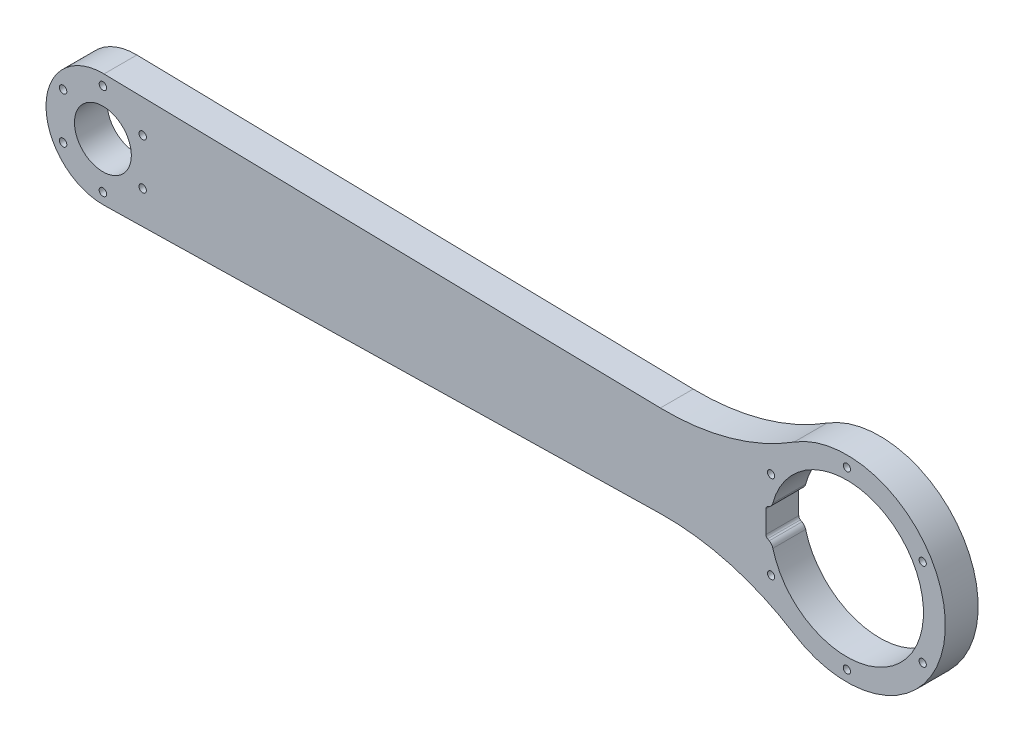
SolidWorks part; units mm, degrees
ref_plane "前视基准面" through (0, 0, 0) normal (0, 0, 1) x (1, 0, 0)
ref_plane "上视基准面" through (0, 0, 0) normal (0, 1, 0) x (1, 0, 0)
ref_plane "右视基准面" through (0, 0, 0) normal (1, 0, 0) x (0, 0, -1)
sketch "草图1" plane through (0, 0, 0) normal (0, 0, 1) x (1, 0, 0)
  line L0 (0, 0) -> (0, 46.9214) construction
  line L1 (0, 0) -> (75.8039, 0) construction
  line L2 (-85.2451, 20.9004) -> (-339.4791, 25.9948)
  line L3 (-85.2451, -20.9004) -> (-339.4791, -25.9948)
  line L4 (-35.5001, 6.7904) -> (-36.238, 6.3734)
  line L5 (-37, 5.0675) -> (-37, -5.0675)
  line L7 (-358.1865, 10.5) -> (-358.1865, -10.5) construction
  line L8 (-30.9669, 5.9447) -> (-28.6669, 5.9455) construction
  line L9 (-35.5001, -6.7904) -> (-36.238, -6.3734)
  line L10 (-29.6741, 7.5384) -> (-26.4741, 7.5394) construction
  line L11 (-340, -21) -> (-321.8135, -10.5) construction
  line L12 (-321.8135, -10.5) -> (-321.8135, 10.5) construction
  line L13 (-321.8135, 10.5) -> (-340, 21) construction
  line L14 (-340, 21) -> (-358.1865, 10.5) construction
  line L15 (-358.1865, -10.5) -> (-340, -21) construction
  circle A0 centre (0, 40) radius 1.65
  arc A1 (0, 38.35) -> (0, 41.65) centre (0, 40) ccw construction
  circle A2 centre (34.641, 20) radius 1.65
  circle A3 centre (34.641, -20) radius 1.65
  arc A4 (34.641, 18.35) -> (34.641, 21.65) centre (34.641, 20) ccw construction
  circle A5 centre (0, -40) radius 1.65
  arc A6 (0, -41.65) -> (0, -38.35) centre (0, -40) ccw construction
  circle A7 centre (-34.641, 20) radius 1.65
  arc A8 (-34.641, 21.65) -> (-34.641, 18.35) centre (-34.641, 20) ccw construction
  circle A9 centre (-34.641, -20) radius 1.65
  circle A10 centre (0, 0) radius 35 construction
  arc A12 (-33.8381, 8.9432) -> (-33.8381, -8.9432) centre (0, 0) cw
  arc A13 (-24.1088, 37.9969) -> (-24.1088, -37.9969) centre (0, 0) cw
  circle A14 centre (-340, 0) radius 13
  arc A15 (-85.2451, -20.9004) -> (-24.1088, -37.9969) centre (-83.0414, -130.8783) cw
  arc A16 (-24.1088, 37.9969) -> (-85.2451, 20.9004) centre (-83.0414, 130.8783) cw
  arc A17 (-339.4791, 25.9948) -> (-339.4791, -25.9948) centre (-340, 0) ccw
  arc A18 (-35.5001, -6.7904) -> (-33.8381, -8.9432) centre (-37.2219, -9.8375) cw
  arc A19 (-33.8381, 8.9432) -> (-35.5001, 6.7904) centre (-37.2219, 9.8375) cw
  arc A20 (-36.238, -6.3734) -> (-37, -5.0675) centre (-35.5, -5.0675) cw
  arc A21 (-36.238, 6.3734) -> (-37, 5.0675) centre (-35.5, 5.0675) ccw
  circle A22 centre (-340, 0) radius 21 construction
  circle A23 centre (-340, 0) radius 18.1865 construction
  circle A24 centre (-340, 21) radius 1.7
  circle A25 centre (-358.1865, 10.5) radius 1.7
  circle A26 centre (-358.1865, -10.5) radius 1.7
  circle A27 centre (-340, -21) radius 1.7
  circle A28 centre (-321.8135, -10.5) radius 1.7
  circle A29 centre (-321.8135, 10.5) radius 1.7
  point P48 (-40.3113, -20)
  point P51 (-40.3113, 20)
  point P60 (-37, 0)
  point P63 (-35, 0)
  point P70 (-34.1789, -7.537)
  point P73 (-34.1789, 7.537)
  point P76 (-37, -5.9428)
  point P79 (-37, 5.9428)
  dimension "D1" = 70
  dimension "D2" = 45
  dimension "D4" = 110
  dimension "D5" = 26
  dimension "D7" = 26
  dimension "D9" = 3.5
  dimension "D10" = 1.5
  dimension "D11" = 42
  dimension "D12" = 3.4
  dimension "D3" = 20
  dimension "D6" = 340
  dimension "D8" = 2
extrude "凸台-拉伸1" add sketch "草图1" along normal blind 15
sketch "草图2" plane through (0, 0, 0) normal (0, 0, 1) x (1, 0, 0)
  line L0 (-376.6145, -430.0012) -> (356.6217, 230.2077) construction
